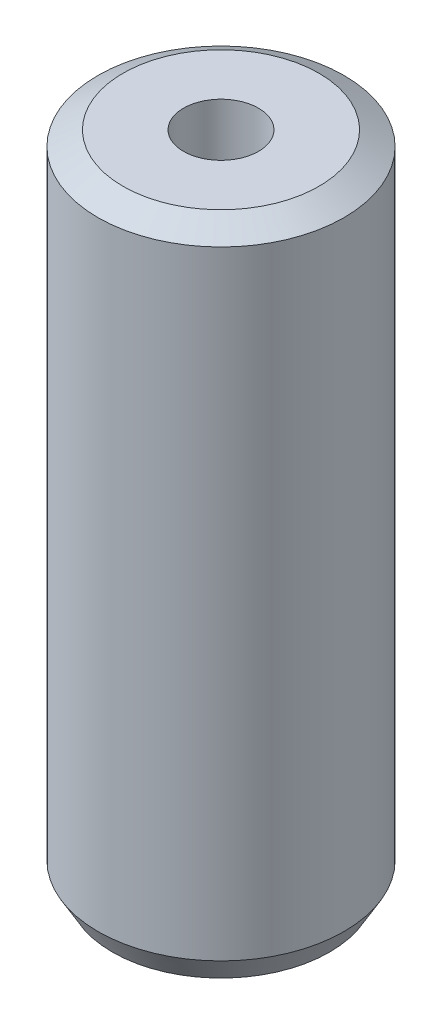
SolidWorks part; units mm, degrees
ref_plane "Front Plane" through (0, 0, 0) normal (0, 0, 1) x (1, 0, 0)
ref_plane "Top Plane" through (0, 0, 0) normal (0, 1, 0) x (1, 0, 0)
ref_plane "Right Plane" through (0, 0, 0) normal (1, 0, 0) x (0, 0, -1)
sketch "Sketch1" plane through (0, 0, 0) normal (0, 1, 0) x (1, 0, 0)
  circle A0 centre (0, 0) radius 10
  dimension "SHAFT_OD" = 20
extrude "Boss-Extrude1" add sketch "Sketch1" along normal blind 53.4445
sketch "Sketch2" plane through (0, 0, 0) normal (0, 1, 0) x (1, 0, 0)
  circle A0 centre (0, 0) radius 3.0448
  dimension "BORE_D" = 6.0896
extrude "Cut-Extrude1" cut sketch "Sketch2" along normal through all
chamfer "Chamfer1" distance 1.1779 angle 60 2 edges at (0, 53.4445, 10) (0, 0, 10) first distance on face at (0, 53.4445, 10) first distance on face at (0, 0, 3.0448)
